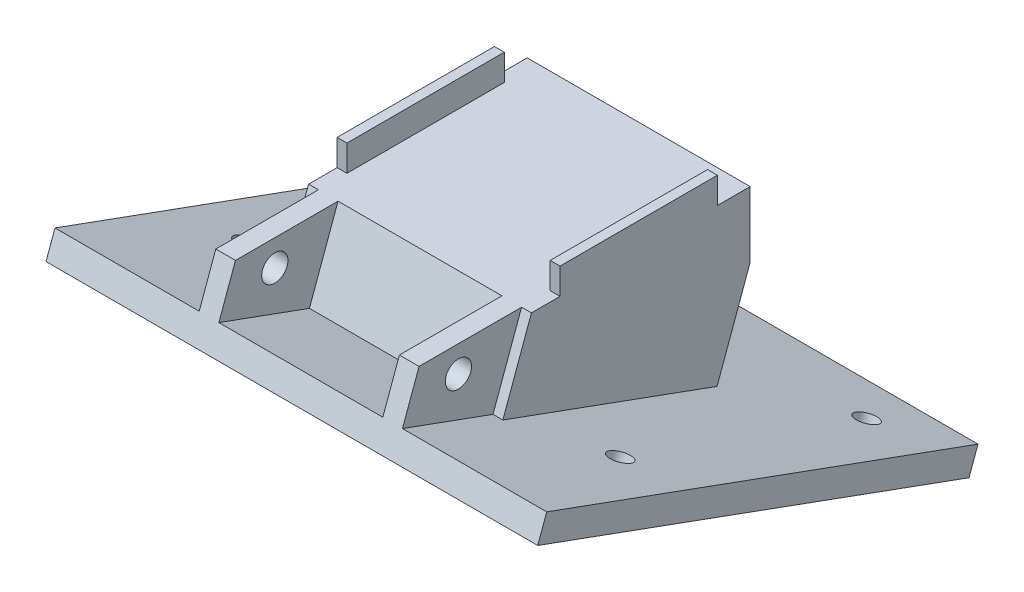
SolidWorks part; units mm, degrees
ref_plane "前视基准面" through (0, 0, 0) normal (0, 0, 1) x (1, 0, 0)
ref_plane "上视基准面" through (0, 0, 0) normal (0, 1, 0) x (1, 0, 0)
ref_plane "右视基准面" through (0, 0, 0) normal (1, 0, 0) x (0, 0, -1)
sketch "草图1" plane through (0, 0, 0) normal (0, 1, 0) x (1, 0, 0)
  line L1 (17, -24.5) -> (-17, -24.5)
  line L2 (17, -24.5) -> (17, 24.5)
  line L3 (17, 24.5) -> (-17, 24.5)
  line L4 (-17, -24.5) -> (-17, 24.5)
  line L5 (0, 24.5) -> (0, -24.5) construction
  line L6 (17, 0) -> (-17, 0) construction
  point P0 (0, 0)
  dimension "D1" = 49
  dimension "D2" = 34
extrude "凸台-拉伸1" add sketch "草图1" along normal blind 10
sketch "草图2" plane through (0, 10, 0) normal (0, 1, 0) x (1, 0, 0)
  line L0 (-17, 24.5) -> (-17, -24.5) construction
  line L1 (-17, 19.5) -> (-15.5, 19.5)
  line L2 (-17, 19.5) -> (-17, -4.5)
  line L3 (-17, -4.5) -> (-15.5, -4.5)
  line L4 (-15.5, 19.5) -> (-15.5, -4.5)
  line L5 (17, 24.5) -> (-17, 24.5) construction
  line L6 (0, -55) -> (0, 55) construction
  line L7 (17, -4.5) -> (15.5, -4.5)
  line L8 (15.5, 19.5) -> (15.5, -4.5)
  line L9 (17, 19.5) -> (17, -4.5)
  line L10 (17, 19.5) -> (15.5, 19.5)
  dimension "D1" = 1.5
  dimension "D2" = 24
  dimension "D3" = 5
extrude "凸台-拉伸2" add sketch "草图2" along normal blind 4
sketch "草图3" plane through (0, 10, 0) normal (0, 1, 0) x (1, 0, 0)
  line L0 (-17, -24.5) -> (17, -24.5) construction
  line L1 (-17, -24.5) -> (-15.5, -24.5)
  line L2 (-17, -24.5) -> (-17, -12.5)
  line L3 (-17, -12.5) -> (-15.5, -12.5)
  line L4 (-15.5, -24.5) -> (-15.5, -12.5)
  line L5 (17, -24.5) -> (15.5, -24.5)
  line L6 (17, -24.5) -> (17, -12.5)
  line L7 (17, -12.5) -> (15.5, -12.5)
  line L8 (15.5, -24.5) -> (15.5, -12.5)
  line L10 (-12.5, -24.5) -> (12.5, -24.5)
  line L11 (-12.5, -24.5) -> (-12.5, -11.5)
  line L12 (-12.5, -11.5) -> (12.5, -11.5)
  line L13 (12.5, -24.5) -> (12.5, -11.5)
  dimension "D1" = 1.5
  dimension "D2" = 1.5
  dimension "D3" = 12
  dimension "D4" = 12
  dimension "D5" = 13
  dimension "D6" = 3
  dimension "D7" = 3
extrude "切除-拉伸1" cut sketch "草图3" against normal up to surface (10 mm away) up to face at (0, 0, 0)
sketch "草图4" plane through (-15.5, 0, 0) normal (-1, 0, 0) x (0, 0, 1)
  line L0 (24.5, 0) -> (24.5, 10) construction
  line L1 (24.5, 10) -> (12.5, 10) construction
  circle A0 centre (18.5, 6) radius 2
  dimension "D1" = 6
  dimension "D2" = 4
  dimension "D3" = 4
extrude "切除-拉伸2" cut sketch "草图4" against normal up to surface (31 mm away) up to face at (15.5, 5, 18.5)
sketch "草图5" plane through (0, 0, 0) normal (0, -1, 0) x (1, 0, 0)
  line L0 (-12.5, 11.5) -> (12.5, 11.5) construction
  line L1 (4, 11.5) -> (-4, 11.5)
  line L2 (4, 11.5) -> (4, 41.5)
  line L4 (-4, 11.5) -> (-4, 41.5)
  line L5 (13, 41.5) -> (4, 41.5)
  line L7 (13, 41.5) -> (13, 56.5)
  line L8 (13, 56.5) -> (-13, 56.5)
  line L9 (-13, 41.5) -> (-13, 56.5)
  line L10 (-4, 41.5) -> (-13, 41.5)
  point P6 (0, 11.5)
  dimension "D1" = 8
  dimension "D2" = 30
  dimension "D3" = 26
  dimension "D4" = 15
  dimension "D5" = 9
extrude "凸台-拉伸3" add sketch "草图5" against normal blind 8
extrude "切除-拉伸4" cut sketch "草图5<2>" against normal up to surface (10 mm away) up to face at (0, 10, 3.1)
sketch "草图5<2>" plane through (0, 0, 0) normal (0, -1, 0) x (1, 0, 0) same geometry as "草图5"
ref_plane "基准面1" through (0, -7.8741, 2.866) normal (0, -0.9397, 0.342) x (1, 0, 0)
sketch "草图7" plane through (-15.5, 0, 0) normal (-1, 0, 0) x (0, 0, 1)
  line L0 (24.5, 10) -> (27.7139, 1.1698)
  line L1 (27.7139, 1.1698) -> (24.5, 0)
  line L2 (12.5, 0) -> (24.5, 0) construction
  line L3 (24.5, 0) -> (24.5, 10) construction
  line L4 (24.5, 0) -> (24.5, 10)
  dimension "D1" = 20
  dimension "D2" = 70
extrude "凸台-拉伸4" add sketch "草图7" against normal blind 3
sketch "草图8" plane through (15.5, 0, 0) normal (1, 0, 0) x (0, 0, -1)
  line L0 (-27.7139, 1.1698) -> (-24.5, 0) construction
  line L1 (-24.5, 10) -> (-27.7139, 1.1698) construction
  line L2 (-24.5, 0) -> (-24.5, 10) construction
  line L3 (-27.7139, 1.1698) -> (-24.5, 0)
  line L4 (-24.5, 10) -> (-27.7139, 1.1698)
  line L5 (-24.5, 0) -> (-24.5, 10)
extrude "凸台-拉伸5" add sketch "草图8" against normal blind 3
sketch "草图9" plane through (15.5, 0, 0) normal (1, 0, 0) x (0, 0, -1)
  line L0 (-12.5, 0) -> (-24.5, 0)
  line L1 (-24.5, 0) -> (-12.5, 0) construction
  line L2 (-24.5, 0) -> (-13.9037, -3.8567)
  line L3 (-13.9037, -3.8567) -> (-12.5, 0)
  dimension "D1" = 20
  dimension "D2" = 70
extrude "凸台-拉伸6" add sketch "草图9" against normal blind 3
sketch "草图10" plane through (17, 0, 0) normal (1, 0, 0) x (0, 0, -1)
  line L0 (-12.5, 0) -> (-13.9037, -3.8567)
  line L1 (-13.9037, -3.8567) -> (18.7681, -15.7483)
  line L2 (18.7681, -15.7483) -> (24.5, 0)
  line L3 (-12.5, 0) -> (24.5, 0) construction
  line L4 (-12.5, 0) -> (24.5, 0)
  line L5 (-13.9037, -3.8567) -> (-12.5, 0) construction
  dimension "D1" = 70
  dimension "D2" = 90
  dimension "D3" = 90
extrude "凸台-拉伸7" add sketch "草图10" against normal up to surface (34 mm away) up to face at (-17, 8.5, -6.75)
sketch "草图11" plane through (-15.5, 0, 0) normal (-1, 0, 0) x (0, 0, 1)
  line L0 (24.5, 0) -> (13.9037, -3.8567) construction
  line L1 (12.5, 0) -> (24.5, 0) construction
  line L2 (13.9037, -3.8567) -> (12.5, 0) construction
  line L3 (24.5, 0) -> (13.9037, -3.8567)
  line L4 (12.5, 0) -> (24.5, 0)
  line L5 (13.9037, -3.8567) -> (12.5, 0)
extrude "凸台-拉伸8" add sketch "草图11" against normal blind 3
sketch "草图12" plane through (-12.5, 0, 0) normal (1, 0, 0) x (0, 0, -1)
  line L0 (-12.5, 0) -> (-11.5, 2.7475)
  line L1 (-11.5, 0) -> (-11.5, 10) construction
  line L2 (-11.5, 2.7475) -> (-11.5, 0)
  line L3 (-11.5, 0) -> (-12.5, 0)
  dimension "D1" = 70
extrude "凸台-拉伸9" add sketch "草图12" along normal up to next
sketch "草图13" plane through (17, 0, 0) normal (1, 0, 0) x (0, 0, -1)
  line L0 (-12.5, 0) -> (-8.8603, 10)
  line L1 (-12.5, 0) -> (-12.5, 10) construction
  line L2 (-12.5, 10) -> (-4.5, 10) construction
  line L3 (-8.8603, 10) -> (-12.5, 10)
  line L4 (-12.5, 10) -> (-12.5, 0)
  dimension "D1" = 70
extrude "切除-拉伸10" cut sketch "草图13" against normal up to surface (1.5 mm away) up to face at (15.5, 6, 20.5)
sketch "草图16" plane through (-17, 0, 0) normal (-1, 0, 0) x (0, 0, 1)
  line L0 (12.5, 10) -> (12.5, 0) construction
  line L1 (8.8603, 10) -> (12.5, 10) construction
  line L2 (12.5, 0) -> (8.8603, 10) construction
  line L3 (12.5, 10) -> (12.5, 0)
  line L4 (8.8603, 10) -> (12.5, 10)
  line L5 (12.5, 0) -> (8.8603, 10)
extrude "切除-拉伸11" cut sketch "草图16" against normal up to surface (1.5 mm away) up to face at (-15.5, 6, 20.5)
sketch "草图17" plane through (-12.5, 0, 0) normal (1, 0, 0) x (0, 0, -1)
  line L0 (-11.5, 2.7475) -> (-11.5, 10)
  line L1 (-11.5, 2.7475) -> (-11.5, 10) construction
  line L2 (-11.5, 10) -> (-8.8603, 10)
  line L3 (-8.8603, 10) -> (-11.5, 2.7475)
  line L4 (-11.5, 2.7475) -> (-13.9037, -3.8567) construction
  dimension "D1" = 70
extrude "切除-拉伸12" cut sketch "草图17" along normal up to surface (25 mm away) up to face at (12.5, 6, 16.5)
sketch "草图18" plane through (0, -7.8741, 2.866) normal (0, -0.9397, 0.342) x (1, 0, 0)
  line L0 (0, 0) -> (0, -35.2803) construction
  line L1 (12.5, 26.4427) -> (15.5, 26.4427) construction
  line L2 (-37.5, 26.4427) -> (37.5, 26.4427)
  line L3 (-37.5, 26.4427) -> (-37.5, -43.5573)
  line L4 (-37.5, -43.5573) -> (37.5, -43.5573)
  line L5 (37.5, 26.4427) -> (37.5, -43.5573)
  line L6 (-37.5, 26.4427) -> (37.5, -43.5573) construction
  line L7 (-37.5, -43.5573) -> (37.5, 26.4427) construction
  line L8 (-28.5, 4.9427) -> (28.5, 4.9427) construction
  line L9 (-28.5, 4.9427) -> (-28.5, -35.0573) construction
  line L10 (-28.5, -35.0573) -> (28.5, -35.0573) construction
  line L11 (28.5, 4.9427) -> (28.5, -35.0573) construction
  line L12 (-28.5, 4.9427) -> (28.5, -35.0573) construction
  line L13 (-28.5, -35.0573) -> (28.5, 4.9427) construction
  circle A0 centre (28.5, 4.9427) radius 1.65
  circle A1 centre (28.5, -35.0573) radius 1.65
  circle A2 centre (-28.5, 4.9427) radius 1.65
  circle A3 centre (-28.5, -35.0573) radius 1.65
  point P3 (0, -15.0573)
  point P4 (0, -8.5573)
  dimension "D6" = 3.3
  dimension "D1" = 75
  dimension "D2" = 70
  dimension "D3" = 57
  dimension "D4" = 40
  dimension "D5" = 28.5
extrude "凸台-拉伸10" add sketch "草图18" along normal mid plane 4
